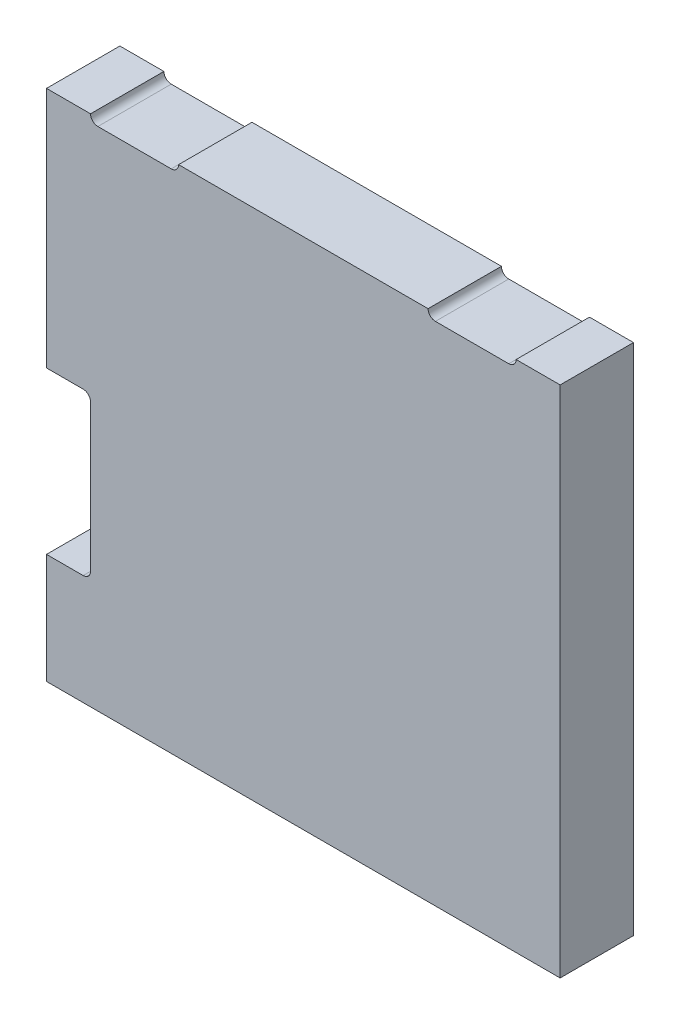
SolidWorks part; units mm, degrees
ref_plane "Front" through (0, 0, 0) normal (0, 0, 1) x (1, 0, 0)
ref_plane "Top" through (0, 0, 0) normal (0, 1, 0) x (1, 0, 0)
ref_plane "Right" through (0, 0, 0) normal (1, 0, 0) x (0, 0, -1)
sketch "草图4" plane through (0, 0, 0) normal (0, 0, 1) x (1, 0, 0)
  line L1 (-35, 35) -> (35, 35)
  line L2 (-35, 35) -> (-35, -35)
  line L3 (-35, -35) -> (35, -35)
  line L4 (35, 35) -> (35, -35)
  line L5 (-35, 35) -> (35, -35) construction
  line L6 (-35, -35) -> (35, 35) construction
  line L7 (-35, 2) -> (-29, 2)
  line L8 (-35, 2) -> (-35, -20)
  line L9 (-35, -20) -> (-29, -20)
  line L10 (-29, 2) -> (-29, -20)
  line L11 (-32, -20) -> (-32, 2) construction
  line L12 (-35, -9) -> (-29, -9) construction
  line L17 (-29, 35) -> (-17, 35)
  line L18 (-29, 35) -> (-29, 34)
  line L19 (-29, 34) -> (-17, 34)
  line L20 (-17, 35) -> (-17, 34)
  line L21 (-23, 34) -> (-23, 35) construction
  line L22 (-29, 34.5) -> (-17, 34.5) construction
  line L23 (17, 35) -> (29, 35)
  line L24 (17, 35) -> (17, 34)
  line L25 (17, 34) -> (29, 34)
  line L26 (29, 35) -> (29, 34)
  line L27 (23, 34) -> (23, 35) construction
  line L28 (17, 34.5) -> (29, 34.5) construction
  point P0 (0, 0)
  point P70 (23, 34.5)
  point P102 (-32, -9)
  point P135 (-23, 34.5)
  dimension "D1" = 70
  dimension "D2" = 70
  dimension "D3" = 22
  dimension "D4" = 6
  dimension "D5" = 15
  dimension "D6" = 1
  dimension "D7" = 12
  dimension "D8" = 6
  dimension "D9" = 12
  dimension "D10" = 1
  dimension "D11" = 6
extrude "凸台-拉伸1" add sketch "草图4" along normal blind 10 contours L1 L26 L25 L24 L20 L19 L18 L2 L7 L10 L9 L3 L4 region at (0.8904, 0.0759, 0)
fillet "圆角1" radius 1 6 edges at (-29, -20, 5) (-29, 2, 5) (29, 34, 5) (17, 34, 5) (-17, 34, 5) (-29, 34, 5)
